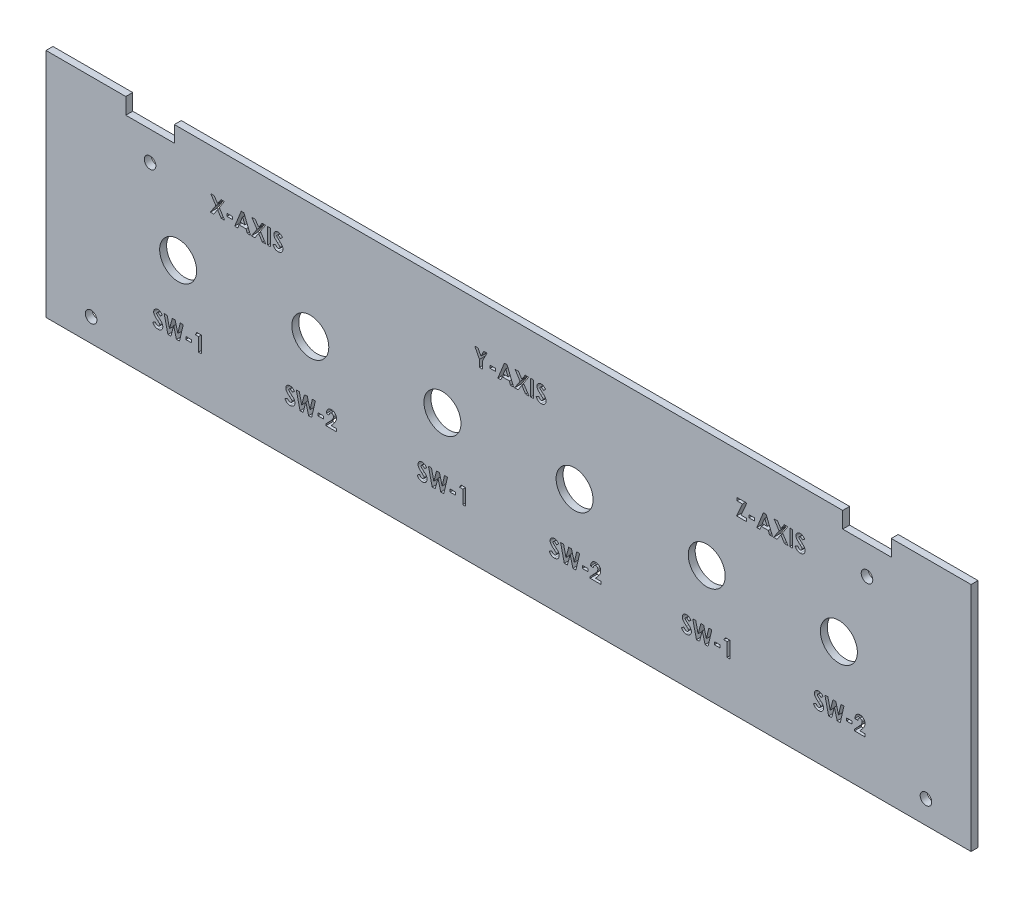
SolidWorks part; units mm, degrees
ref_plane "Front Plane" through (0, 0, 0) normal (0, 0, 1) x (1, 0, 0)
ref_plane "Top Plane" through (0, 0, 0) normal (0, 1, 0) x (1, 0, 0)
ref_plane "Right Plane" through (0, 0, 0) normal (1, 0, 0) x (0, 0, -1)
sketch "Sketch1" plane through (0, 0, 0) normal (0, 0, 1) x (1, 0, 0)
  line L1 (-200, -50) -> (200, -50)
  line L2 (-200, -50) -> (-200, 50)
  line L3 (-200, 50) -> (200, 50)
  line L4 (200, -50) -> (200, 50)
  point P5 (0, 50)
  point P6 (200, 0)
  dimension "D1" = 400
  dimension "D2" = 100
extrude "Boss-Extrude1" add sketch "Sketch1" along normal blind 3
sketch "Sketch2" plane through (0, 0, 3) normal (0, 0, 1) x (1, 0, 0)
  line L0 (-150.8571, 0) -> (-77.7171, 0) construction
  line L1 (-142.8571, 0) -> (-85.7171, 0) construction
  line L2 (-200, 50) -> (-200, -50) construction
  line L3 (-36.5771, 0) -> (36.5629, 0) construction
  line L4 (77.7029, 0) -> (150.8429, 0) construction
  line L5 (-114.2871, -1000) -> (-114.2871, 49000) construction
  line L6 (0, -1000) -> (0, 49000) construction
  line L7 (114.2729, -1000) -> (114.2729, 49000) construction
  line L8 (-150.8571, 25) -> (-77.7171, 25) construction
  line L9 (-36.57, 25) -> (36.57, 25) construction
  line L10 (150.8571, 25) -> (77.7171, 25) construction
  line L11 (200, 50) -> (-200, 50) construction
  line L12 (-160.8541, -30) -> (-124.8602, -30) construction
  line L13 (-103.7141, -30) -> (-67.7202, -30) construction
  line L14 (-46.5741, -30) -> (-10.5802, -30) construction
  line L15 (10.5659, -30) -> (46.5598, -30) construction
  line L16 (67.7059, -30) -> (103.6998, -30) construction
  line L17 (124.8459, -30) -> (160.8398, -30) construction
  line L18 (-160.8541, -30) -> (-103.7141, -30) construction
  circle A0 centre (-142.8571, 0) radius 8
  circle A1 centre (-85.7171, 0) radius 8
  circle A2 centre (-28.5771, 0) radius 8
  circle A3 centre (28.5629, 0) radius 8
  circle A4 centre (85.7029, 0) radius 8
  circle A5 centre (142.8429, 0) radius 8
  text T0 "<b>X-AXIS</b>" font "Century Gothic" height 7
  text T1 "<b>Y-AXIS</b>" font "Century Gothic" height 7
  text T2 "<b>Z-AXIS</b>" font "Century Gothic" height 7
  text T3 "<b>SW-1</b>" font "Century Gothic" height 7
  text T4 "<b>SW-2</b>" font "Century Gothic" height 7
  text T5 "<b>SW-1</b>" font "Century Gothic" height 7
  text T6 "<b>SW-1</b>" font "Century Gothic" height 7
  text T7 "<b>SW-2</b>" font "Century Gothic" height 7
  text T8 "<b>SW-2</b>" font "Century Gothic" height 7
  point P26 (-114.2871, 0)
  point P31 (114.2729, 0)
  point P34 (-114.2871, 25)
  point P37 (0, 25)
  point P49 (-142.8571, -30)
  dimension "D1" = 16
  dimension "D3" = 57.14
  dimension "D4" = 57.1429
  dimension "D5" = 25
  dimension "D6" = 30
  dimension "D8" = 57.14
  dimension "D2" = 6
  dimension "D7" = 6
extrude "Cut-Extrude1" cut sketch "Sketch2" against normal through all
sketch "Sketch3" plane through (0, 0, 3) normal (0, 0, 1) x (1, 0, 0)
  line L0 (0, -1000) -> (0, 49000) construction
  line L1 (200, -50) -> (200, 50) construction
  line L2 (200, 50) -> (-200, 50) construction
  circle A0 centre (155, 30.5) radius 2.5
  circle A1 centre (-155, 30.5) radius 2.5
  dimension "D3" = 5
  dimension "D1" = 45
  dimension "D2" = 19.5
extrude "Cut-Extrude2" cut sketch "Sketch3" against normal up to next (3 mm away)
sketch "Sketch4" plane through (0, 0, 3) normal (0, 0, 1) x (1, 0, 0)
  line L0 (0, -1000) -> (0, 49000) construction
  line L1 (200, -50) -> (200, 50) construction
  line L2 (-200, -50) -> (200, -50) construction
  circle A0 centre (180.5, -40) radius 2.5
  circle A1 centre (-180.5, -40) radius 2.5
  dimension "D1" = 19.5
  dimension "D2" = 10
  dimension "D3" = 5
extrude "Cut-Extrude3" cut sketch "Sketch4" against normal through all
sketch "Sketch5" plane through (0, 0, 3) normal (0, 0, 1) x (1, 0, 0)
  line L0 (0, -1000) -> (0, 49000) construction
  line L1 (-155, -969.5) -> (-155, 49030.5) construction
  line L2 (200, 50) -> (-200, 50) construction
  line L3 (-165.5, 43) -> (-144.5, 43)
  line L4 (-165.5, 43) -> (-165.5, 50)
  line L5 (-165.5, 50) -> (-144.5, 50)
  line L6 (-144.5, 43) -> (-144.5, 50)
  line L7 (-165.5, 43) -> (-144.5, 50) construction
  line L8 (-165.5, 50) -> (-144.5, 43) construction
  line L9 (165.5, 50) -> (144.5, 43) construction
  line L10 (165.5, 43) -> (144.5, 50) construction
  line L11 (144.5, 43) -> (144.5, 50)
  line L12 (165.5, 50) -> (144.5, 50)
  line L13 (165.5, 43) -> (165.5, 50)
  line L14 (165.5, 43) -> (144.5, 43)
  point P4 (-155, 46.5)
  point P17 (155, 46.5)
  dimension "D1" = 21
  dimension "D2" = 7
extrude "Cut-Extrude4" cut sketch "Sketch5" against normal up to next (3 mm away)
